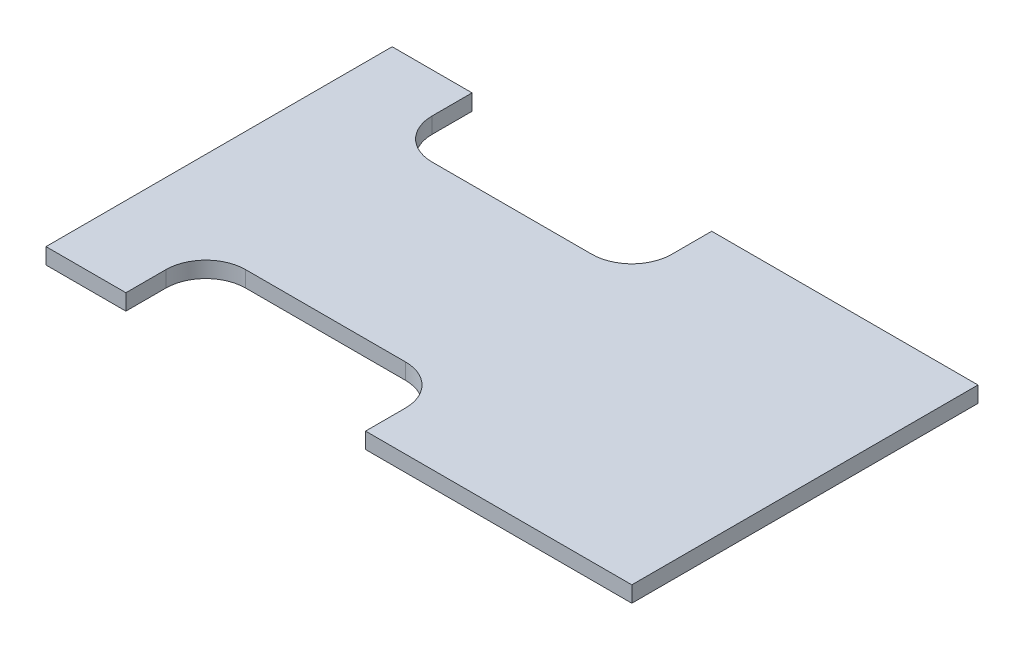
SolidWorks part; units mm, degrees
material "ABS"
ref_plane "Front Plane" through (0, 0, 0) normal (0, 0, 1) x (1, 0, 0)
ref_plane "Top Plane" through (0, 0, 0) normal (0, 1, 0) x (1, 0, 0)
ref_plane "Right Plane" through (0, 0, 0) normal (1, 0, 0) x (0, 0, -1)
sketch "Sketch1" plane through (0, 0, 0) normal (0, 1, 0) x (1, 0, 0)
  line L1 (-110, 65) -> (110, 65)
  line L2 (-110, 65) -> (-110, -65)
  line L3 (-110, -65) -> (110, -65)
  line L4 (110, 65) -> (110, -65)
  line L5 (-110, 65) -> (110, -65) construction
  line L6 (-110, -65) -> (110, 65) construction
  point P0 (0, 0)
  dimension "D1" = 220
  dimension "D2" = 130
extrude "Boss-Extrude1" add sketch "Sketch1" along normal blind 6
sketch "Sketch2" plane through (0, 6, 0) normal (0, 1, 0) x (1, 0, 0)
  line L0 (-110, -65) -> (-80, -65) construction
  line L1 (-110, -65) -> (110, -65) construction
  line L2 (0, 0) -> (-110, 0) construction
  line L3 (-80, -65) -> (10, -65)
  line L4 (-80, -65) -> (-80, -35)
  line L5 (-80, -35) -> (10, -35)
  line L6 (10, -65) -> (10, -35)
  line L7 (-110, 65) -> (-110, -65) construction
  line L8 (-80, 35) -> (10, 35)
  line L9 (10, 65) -> (10, 35)
  line L10 (-80, 65) -> (10, 65)
  line L11 (-80, 65) -> (-80, 35)
  dimension "D1" = 30
  dimension "D2" = 90
  dimension "D3" = 30
extrude "Cut-Extrude1" cut sketch "Sketch2" against normal through all
fillet "Fillet1" radius 15 4 edges at (10, 3, -35) (-80, 3, -35) (-80, 3, 35) (10, 3, 35)
